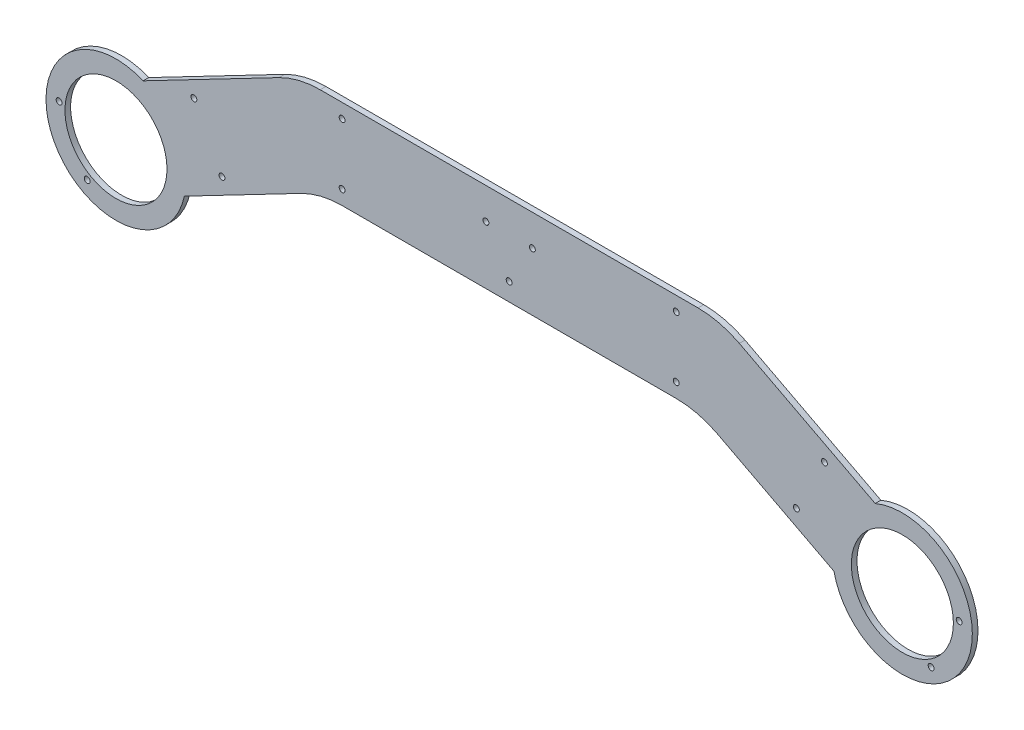
SolidWorks part; units mm, degrees
material "6061-T6 (SS)"
ref_plane "Front Plane" through (0, 0, 0) normal (0, 0, 1) x (1, 0, 0)
ref_plane "Top Plane" through (0, 0, 0) normal (0, 1, 0) x (1, 0, 0)
ref_plane "Right Plane" through (0, 0, 0) normal (1, 0, 0) x (0, 0, -1)
sketch "Sketch1" plane through (0, 0, 0) normal (0, 0, 1) x (1, 0, 0)
  line L0 (0, -33.2132) -> (0, -83.2132) construction
  line L1 (105.7091, -33.2132) -> (-105.7091, -33.2132)
  line L2 (-128.7965, -38.8627) -> (-262.5891, -108.5107)
  line L3 (-262.5891, -108.5107) -> (-239.5017, -152.8612)
  line L4 (-239.5017, -152.8612) -> (-116.5616, -88.8627)
  line L5 (-93.4741, -83.2132) -> (93.4741, -83.2132)
  line L6 (116.5616, -88.8627) -> (239.5017, -152.8612)
  line L7 (239.5017, -152.8612) -> (262.5891, -108.5107)
  line L8 (262.5891, -108.5107) -> (128.7965, -38.8627)
  line L9 (-117.944, -33.2132) -> (0, 28.1845) construction
  line L10 (0, 28.1845) -> (117.944, -33.2132) construction
  line L11 (-251.0454, -130.686) -> (-220, -114.5248) construction
  line L12 (251.0454, -130.686) -> (220, -114.5248) construction
  line L13 (-330, -114.5248) -> (-110, -114.5248) construction
  line L14 (-110, -114.5248) -> (110, -114.5248) construction
  line L15 (0, 0) -> (17.6777, -17.6777) construction
  line L16 (28.2843, -7.0711) -> (7.0711, -28.2843) construction
  line L17 (-7.0711, -28.2843) -> (-17.6777, -17.6777) construction
  line L18 (-17.6777, -17.6777) -> (17.6777, 17.6777) construction
  line L19 (17.6777, 17.6777) -> (28.2843, 7.0711) construction
  line L20 (17.6777, 17.6777) -> (67.5526, 17.6777) construction
  line L21 (0, -35.3553) -> (35.3553, 0) construction
  line L22 (0, 0) -> (6.4096, -24.1644) construction
  line L23 (-8.089, -28.0102) -> (20.9083, -20.3186) construction
  circle A1 centre (0, 0) radius 7.9375 construction
  circle A2 centre (-220, -114.5248) radius 110 construction
  circle A3 centre (220, -114.5248) radius 110 construction
  arc A4 (28.2843, -7.0711) -> (28.2843, 7.0711) centre (21.2132, 0) ccw construction
  arc A5 (7.0711, -28.2843) -> (-7.0711, -28.2843) centre (0, -21.2132) cw construction
  arc A6 (93.4741, -83.2132) -> (116.5616, -88.8627) centre (93.4741, -133.2132) cw
  arc A7 (-116.5616, -88.8627) -> (-93.4741, -83.2132) centre (-93.4741, -133.2132) cw
  arc A8 (128.7965, -38.8627) -> (105.7091, -33.2132) centre (105.7091, -83.2132) ccw
  arc A9 (-105.7091, -33.2132) -> (-128.7965, -38.8627) centre (-105.7091, -83.2132) ccw
  circle A10 centre (0, 0) radius 7.9375 construction
  arc A11 (20.9083, -20.3186) -> (28.0102, -8.089) centre (18.3444, -10.6528) ccw construction
  point P26 (17.6777, -17.6777)
  point P33 (35.3553, 0)
  point P36 (0, -35.3553)
  point P40 (0, -31.2132)
  dimension "D12" = 50
  dimension "D2" = 220
  dimension "D1" = 50
  dimension "D3" = 125
  dimension "D5" = 35
  dimension "D8" = 45
  dimension "D10" = 2
extrude "Base" add sketch "Sketch1" along normal blind 3.175
fillet "Fillet1" radius 10 4 edges at (262.5891, -108.5107, 1.5875) (239.5017, -152.8612, 1.5875) (-239.5017, -152.8612, 1.5875) (-262.5891, -108.5107, 1.5875)
sketch "Sketch2" plane through (0, 0, 3.175) normal (0, 0, 1) x (1, 0, 0)
  line L0 (0, -33.2132) -> (0, -83.2132) construction
  line L1 (105.7091, -33.2132) -> (-105.7091, -33.2132) construction
  line L2 (-93.4741, -83.2132) -> (93.4741, -83.2132) construction
  circle A0 centre (0, -58.2132) radius 15 construction
  circle A1 centre (-12.9904, -50.7132) radius 1.65
  circle A2 centre (12.9904, -50.7132) radius 1.65
  circle A3 centre (0, -73.2132) radius 1.65
  point P17 (0, -58.2132)
  dimension "D1" = 30
  dimension "D2" = 3.3
  dimension "D3" = 3
extrude "Adapter Attachment" cut sketch "Sketch2" against normal through all
sketch "Sketch3" plane through (0, 0, 3.175) normal (0, 0, 1) x (1, 0, 0)
  line L0 (-258.6387, -109.7562) -> (-249.1015, -112.7633) construction
  line L1 (-238.2561, -148.9108) -> (-235.249, -139.3736) construction
  line L2 (-251.799, -111.9128) -> (-255.493, -104.8167) construction
  line L3 (-236.0996, -142.0711) -> (-232.4056, -149.1672) construction
  line L4 (-128.7965, -38.8627) -> (-253.719, -103.8932) construction
  line L5 (-230.6316, -148.2437) -> (-116.5616, -88.8627) construction
  line L6 (0, -1.7463) -> (0, 1.7463) construction
  line L7 (-236.0996, -142.0711) -> (-160.7036, -102.8225) construction
  line L8 (-176.4031, -72.6641) -> (-251.799, -111.9128) construction
  line L9 (-93.4741, -83.2132) -> (-93.4741, -75.2132) construction
  line L10 (-93.4741, -83.2132) -> (93.4741, -83.2132) construction
  line L11 (-93.4741, -41.2132) -> (-93.4741, -33.2132) construction
  line L12 (105.7091, -33.2132) -> (-105.7091, -33.2132) construction
  arc A0 (-253.719, -103.8932) -> (-257.9716, -117.3808) centre (-249.1015, -112.7633) ccw construction
  arc A1 (-244.1191, -143.9911) -> (-230.6316, -148.2437) centre (-235.249, -139.3736) ccw construction
  circle A2 centre (-251.799, -111.9128) radius 1.65
  circle A3 centre (-236.0996, -142.0711) radius 1.65
  circle A4 centre (-160.7036, -102.8225) radius 1.65
  circle A5 centre (-176.4031, -72.6641) radius 1.65
  circle A6 centre (-93.4741, -75.2132) radius 1.65
  circle A7 centre (-93.4741, -41.2132) radius 1.65
  circle A8 centre (93.4741, -41.2132) radius 1.65
  circle A9 centre (93.4741, -75.2132) radius 1.65
  circle A10 centre (176.4031, -72.6641) radius 1.65
  circle A11 centre (160.7036, -102.8225) radius 1.65
  circle A12 centre (251.799, -111.9128) radius 1.65
  circle A13 centre (236.0996, -142.0711) radius 1.65
  dimension "D2" = 3.3
  dimension "D1" = 8
  dimension "D4" = 85
extrude "Strut Holes" cut sketch "Sketch3" against normal through all
sketch "Sketch4" plane through (0, 0, 3.175) normal (0, 0, 1) x (1, 0, 0)
  line L0 (-241.4586, -107.7589) -> (-213.2341, -93.0661) construction
  line L1 (-128.7965, -38.8627) -> (-262.5891, -108.5107) construction
  line L2 (0, -1.7463) -> (0, 1.7463) construction
  circle A0 centre (-220, -114.5248) radius 16.05
  circle A1 centre (-220, -114.5248) radius 22.5 construction
  circle A2 centre (-241.4586, -107.7589) radius 2.75
  circle A3 centre (-213.2341, -93.0661) radius 2.75
  circle A4 centre (-198.5414, -121.2906) radius 2.75
  circle A5 centre (-226.7659, -135.9834) radius 2.75
  circle A6 centre (226.7659, -135.9834) radius 2.75
  circle A7 centre (241.4586, -107.7589) radius 2.75
  circle A8 centre (198.5414, -121.2906) radius 2.75
  circle A9 centre (213.2341, -93.0661) radius 2.75
  circle A10 centre (220, -114.5248) radius 16.05
  point P15 (-220, -114.5248)
  dimension "D1" = 32.1
  dimension "D2" = 45
  dimension "D4" = 5.5
  dimension "D3" = 4
extrude "Motor Connection" [suppressed] cut sketch "Sketch4" against normal through all
sketch "Sketch5" plane through (0, 0, 3.175) normal (0, 0, 1) x (1, 0, 0)
  line L0 (0, -1.7463) -> (0, 1.7463) construction
  circle A0 centre (-220, -114.5248) radius 28.55
  circle A1 centre (-220, -114.5248) radius 39.1548
  arc A2 (-253.719, -103.8932) -> (-257.9716, -117.3808) centre (-249.1015, -112.7633) ccw construction
  circle A3 centre (-236.0996, -142.0711) radius 1.65 construction
  circle A4 centre (-251.799, -111.9128) radius 1.65 construction
  circle A5 centre (-236.0996, -142.0711) radius 1.65
  circle A6 centre (-251.799, -111.9128) radius 1.65
  circle A7 centre (251.799, -111.9128) radius 1.65
  circle A8 centre (236.0996, -142.0711) radius 1.65
  circle A9 centre (220, -114.5248) radius 39.1548
  circle A10 centre (220, -114.5248) radius 28.55
  line M20 (253.719, -103.8932) -> (128.7965, -38.8627)
  line M24 (-128.7965, -38.8627) -> (-253.719, -103.8932)
  line M28 (-230.6316, -148.2437) -> (-116.5616, -88.8627)
  line M32 (116.5616, -88.8627) -> (230.6316, -148.2437)
  dimension "D1" = 57.1
extrude "Motor Ring" add sketch "Sketch5" against normal up to surface (3.175 mm away) up to face at (-250.149, -111.9128, 0)
extrude "Motor Slot" cut sketch "Sketch5<2>" against normal through all contours A0 M24 M28 | A10 M32 M20 region at (-220, -114.5248, 3.175) region at (220, -114.5248, 3.175)
sketch "Sketch5<2>" plane through (0, 0, 3.175) normal (0, 0, 1) x (1, 0, 0) same geometry as "Sketch5"
equation "\"D2@Sketch1\"=\"Wheel Diameter@Rocker Bogie Assy-1.Assembly\""
equation "\"D1@Base\"=\"Plate Thickness@Rocker Bogie Assy-1.Assembly\""
equation "\"D3@Sketch1\"=\"Bogie Angle@Rocker Bogie Assy-1.Assembly\""
